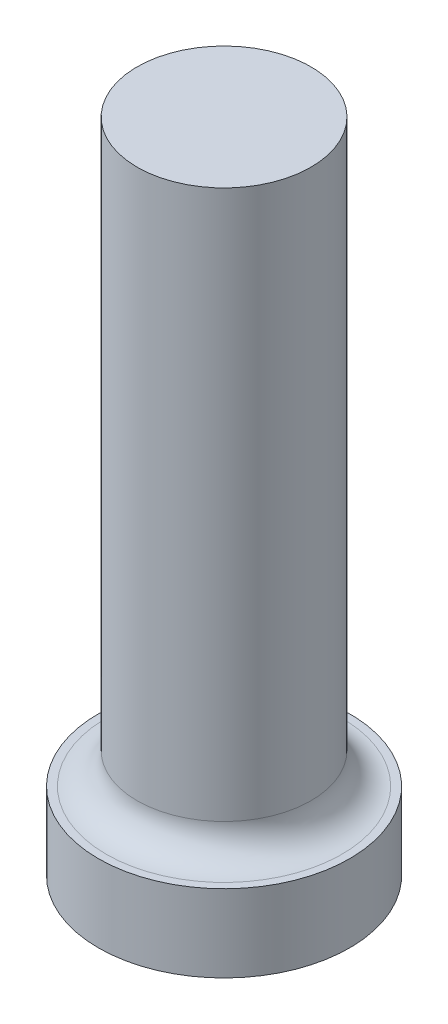
SolidWorks part; units mm, degrees
ref_plane "Front Plane" through (0, 0, 0) normal (0, 0, 1) x (1, 0, 0)
ref_plane "Top Plane" through (0, 0, 0) normal (0, 1, 0) x (1, 0, 0)
ref_plane "Right Plane" through (0, 0, 0) normal (1, 0, 0) x (0, 0, -1)
sketch "Sketch2" plane through (0, 0, 0) normal (0, 1, 0) x (1, 0, 0)
  circle A0 centre (0, 0) radius 2.25
  circle A1 centre (0, 0) radius 3.25
  dimension "D1" = 4.5
  dimension "D2" = 6.5
extrude "Boss-Extrude1" add sketch "Sketch2" along normal blind 15 contours A0 region at (0, 0, 0)
extrude "Boss-Extrude2" add sketch "Sketch2<3>" against normal blind 2 contours A1 A0 | A0 region at (0, 0, 0) region at (-3.1581, 0, 0)
sketch "Sketch2<3>" plane through (0, 0, 0) normal (0, 1, 0) x (1, 0, 0) same geometry as "Sketch2"
fillet "Fillet1" radius 0.8 1 edges at (0, 0, 2.25)
